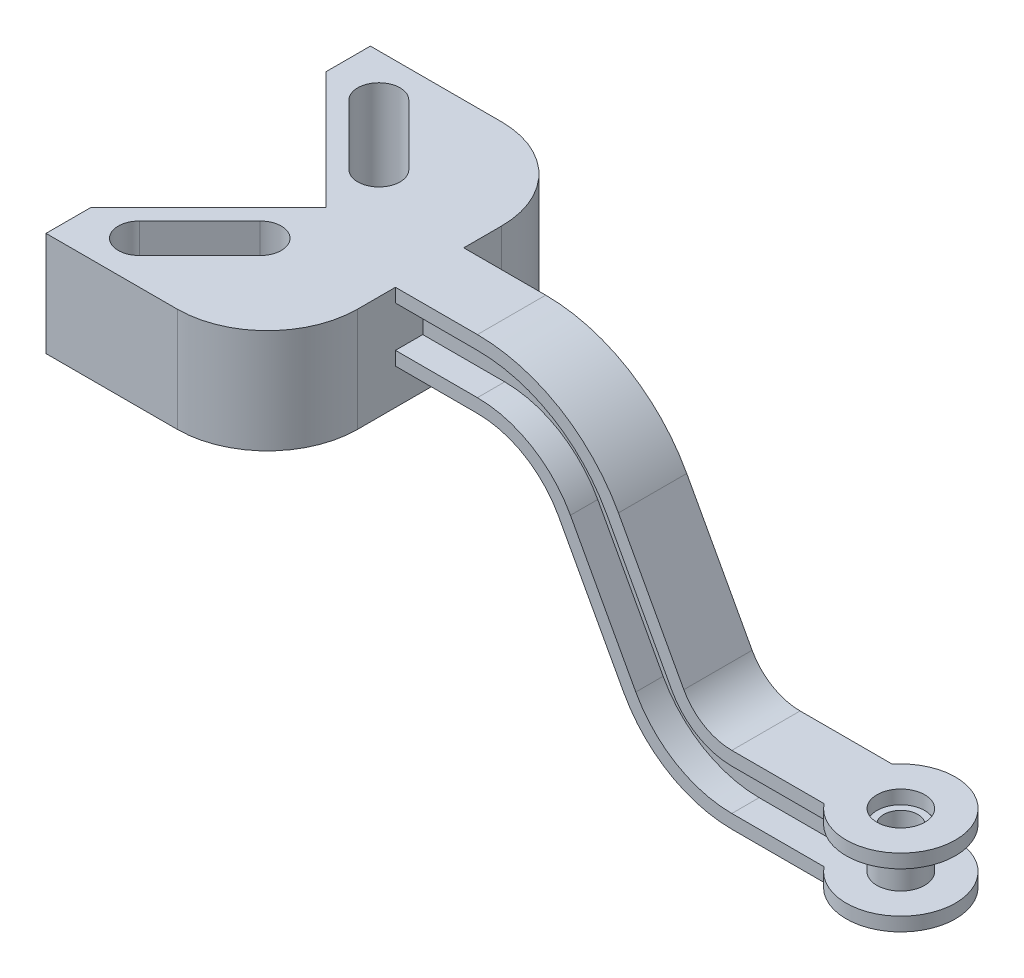
SolidWorks part; units mm, degrees
ref_plane "Front Plane" through (0, 0, 0) normal (0, 0, 1) x (1, 0, 0)
ref_plane "Top Plane" through (0, 0, 0) normal (0, 1, 0) x (1, 0, 0)
ref_plane "Right Plane" through (0, 0, 0) normal (1, 0, 0) x (0, 0, -1)
sketch "Sketch3" plane through (0, 0, 0) normal (0, 0, 1) x (1, 0, 0)
  line L0 (0, 0) -> (120, 0)
  line L1 (308.9505, -112.4197) -> (404.6661, -288.7256)
  line L2 (492.55, -341.0138) -> (627.55, -341.0138)
  line L6 (627.55, -321.0138) -> (627.55, -341.0138)
  line L7 (0, 20) -> (0, 0)
  line L8 (0, 20) -> (120, 20)
  line L9 (326.5273, -102.8774) -> (422.2428, -279.1832)
  line L10 (492.55, -321.0138) -> (627.55, -321.0138)
  line L16 (0, 20) -> (120, 20)
  line L17 (326.5273, -102.8774) -> (422.2428, -279.1832)
  line L18 (0, -60) -> (120, -60)
  line L19 (256.2201, -141.0468) -> (351.9357, -317.3526)
  line L20 (492.55, -401.0138) -> (627.55, -401.0138)
  line L21 (0, 0) -> (0, -60)
  line L22 (627.55, -341.0138) -> (627.55, -401.0138)
  line L23 (0, -80) -> (120, -80)
  line L24 (238.6433, -150.5891) -> (334.3589, -326.895)
  line L25 (492.55, -421.0138) -> (627.55, -421.0138)
  line L26 (0, -60) -> (0, -80)
  line L27 (627.55, -401.0138) -> (627.55, -421.0138)
  arc A0 (120, 0) -> (308.9505, -112.4197) centre (120, -215) cw
  arc A1 (404.6661, -288.7256) -> (492.55, -341.0138) centre (492.55, -241.0138) ccw
  arc A4 (120, 20) -> (326.5273, -102.8774) centre (120, -215) cw
  arc A5 (422.2428, -279.1832) -> (492.55, -321.0138) centre (492.55, -241.0138) ccw
  arc A8 (120, 20) -> (326.5273, -102.8774) centre (120, -215) cw
  arc A9 (120, -60) -> (256.2201, -141.0468) centre (120, -215) cw
  arc A10 (351.9357, -317.3526) -> (492.55, -401.0138) centre (492.55, -241.0138) ccw
  arc A11 (120, -80) -> (238.6433, -150.5891) centre (120, -215) cw
  arc A12 (334.3589, -326.895) -> (492.55, -421.0138) centre (492.55, -241.0138) ccw
  dimension "D2" = 215
  dimension "D3" = 100
  dimension "D1" = 120
  dimension "D4" = 135
  dimension "D5" = 627.55
  dimension "D9" = 20
  dimension "D6" = 20
  dimension "D7" = 20
  dimension "D8" = 60
extrude "Boss-Extrude1" add sketch "Sketch3" along normal mid plane 20 contours L19 A10 L20 L22 L2 A1 L1 A0 L0 L21 L18 A9 region at (315.8708, -198.9283, 0)
extrude "Boss-Extrude2" add sketch "Sketch3<3>" along normal mid plane 100 contours A5 L9 A4 L8 L7 L0 A0 L1 A1 L2 L6 L10 | L24 A12 L25 L27 L20 A10 L19 A9 L18 L26 L23 A11 region at (7.2398, 10, 0) region at (310.5382, -245.9113, 0)
sketch "Sketch3<3>" plane through (0, 0, 0) normal (0, 0, 1) x (1, 0, 0) same geometry as "Sketch3"
sketch "Sketch5" plane through (0, 0, 0) normal (0, 1, 0) x (1, 0, 0)
  line L0 (0, 105.5) -> (0, -105.5)
  line L1 (-132, -237.5) -> (-324.2014, -237.5)
  line L2 (-324.2014, -237.5) -> (-324.2014, -172.5)
  line L3 (-324.2014, -172.5) -> (-151.7014, 0)
  line L4 (-151.7014, 0) -> (0, 0) construction
  line L5 (-249.5986, -175.3155) -> (-161.2102, -86.9272) construction
  line L11 (-132, 237.5) -> (-324.2014, 237.5)
  line L12 (-324.2014, 237.5) -> (-324.2014, 172.5)
  line L13 (-324.2014, 172.5) -> (-151.7014, 0)
  line L14 (-271.5189, -153.3952) -> (-183.1305, -65.0068)
  line L15 (-227.6783, -197.2358) -> (-139.2899, -108.8475)
  line L16 (-249.5986, 175.3155) -> (-161.2102, 86.9272) construction
  line L17 (-271.5189, 153.3952) -> (-183.1305, 65.0068)
  line L18 (-227.6783, 197.2358) -> (-139.2899, 108.8475)
  line L19 (0, 0) -> (690, 0) construction
  line L21 (656.459, 10) -> (610.6275, 10)
  line L22 (656.459, -10) -> (610.6275, -10)
  arc A2 (0, -105.5) -> (-132, -237.5) centre (-132, -105.5) cw
  arc A3 (0, 105.5) -> (-132, 237.5) centre (-132, 105.5) ccw
  arc A4 (-271.5189, -153.3952) -> (-227.6783, -197.2358) centre (-249.5986, -175.3155) ccw
  arc A5 (-139.2899, -108.8475) -> (-183.1305, -65.0068) centre (-161.2102, -86.9272) ccw
  arc A6 (-271.5189, 153.3952) -> (-227.6783, 197.2358) centre (-249.5986, 175.3155) cw
  arc A7 (-139.2899, 108.8475) -> (-183.1305, 65.0068) centre (-161.2102, 86.9272) cw
  circle A8 centre (690, 0) radius 80
  circle A9 centre (690, 0) radius 25
  circle A10 centre (690, 0) radius 35
  point P4 (0, 0)
  point P11 (-205.4044, -131.1213)
  point P21 (-205.4044, 131.1213)
  point P36 (655, 0)
  dimension "D4" = 690
  dimension "D5" = 132
  dimension "D2" = 62
  dimension "D8" = 160
  dimension "D9" = 50
  dimension "D10" = 70
  dimension "D1" = 125
  dimension "D3" = 65
  dimension "D6" = 90
  dimension "D7" = 475
extrude "Boss-Extrude5" add sketch "Sketch5" against normal blind 152.5 from surface contours L0 A3 L11 L12 L13 L3 L2 L1 A2 A5 L15 A4 L14 L18 A7 L17 A6 region at (-130.0344, 0, 0) starting at face at (60, 20, 0)
extrude "Boss-Extrude6" add sketch "Sketch5<3>" along normal blind 20 from surface contours A8 A10 | A10 L21 A8 L22 region at (632.8472, 0, 0) region at (633.5432, 0, -12.2583) starting at face at (560.05, -421.0138, 0)
sketch "Sketch5<3>" plane through (0, 0, 0) normal (0, 1, 0) x (1, 0, 0) same geometry as "Sketch5"
extrude "Boss-Extrude7" add sketch "Sketch5<4>" against normal blind 20 from surface contours A8 A10 | A10 L21 A8 L22 region at (632.8472, 0, 0) region at (633.5432, 0, -12.2583) starting at face at (560.05, -321.0138, 0)
sketch "Sketch5<4>" plane through (0, 0, 0) normal (0, 1, 0) x (1, 0, 0) same geometry as "Sketch5"
extrude "Boss-Extrude8" add sketch "Sketch5<5>" along normal blind 60 from surface separate body contours A10 A9 | A10 L21 A8 L22 region at (632.8472, 0, 0) region at (694.91, 0, -33.6538) starting at face at (543.175, -401.0138, 6.25)
sketch "Sketch5<5>" plane through (0, 0, 0) normal (0, 1, 0) x (1, 0, 0) same geometry as "Sketch5"
